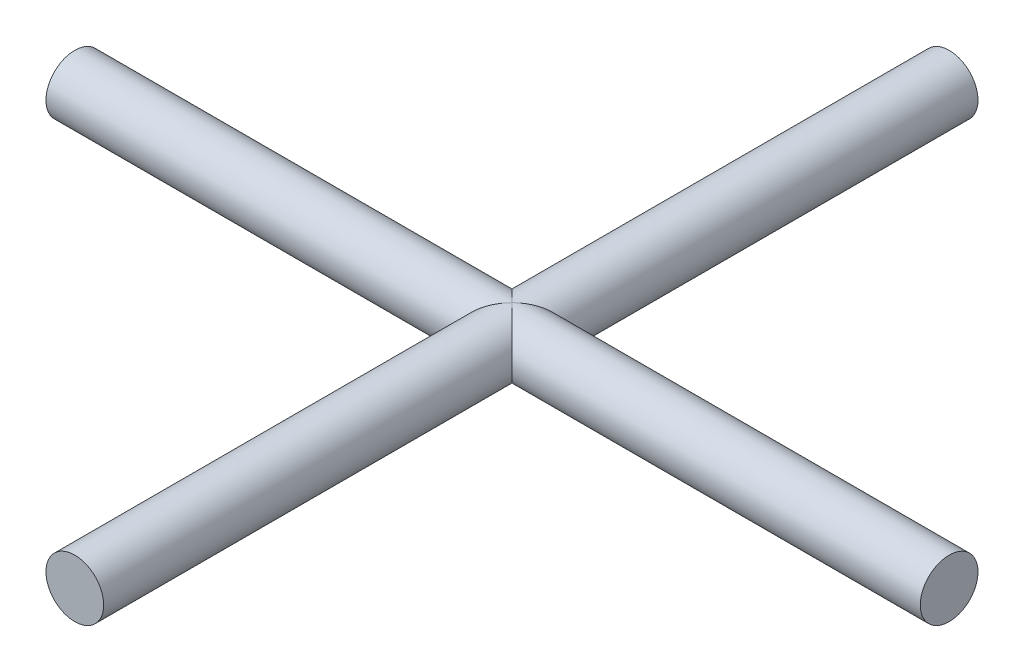
SolidWorks part; units mm, degrees
ref_plane "Front Plane" through (0, 0, 0) normal (0, 0, 1) x (1, 0, 0)
ref_plane "Top Plane" through (0, 0, 0) normal (0, 1, 0) x (1, 0, 0)
ref_plane "Right Plane" through (0, 0, 0) normal (1, 0, 0) x (0, 0, -1)
ref_axis "Axis1" through (0, -2.7225, 0) along (0, 1, 0)
sketch "Sketch2" plane through (0, 0, 0) normal (0, 0, 1) x (1, 0, 0)
  circle A0 centre (0, 0) radius 2.475
  dimension "D1" = 4.95
extrude "Boss-Extrude1" add sketch "Sketch2" along normal blind 37.5 and the other way blind 37.5
pattern_circular "CirPattern1" count 2 every 90 about axis through (0, -2.7225, 0) along (0, 1, 0) of "Boss-Extrude1"
